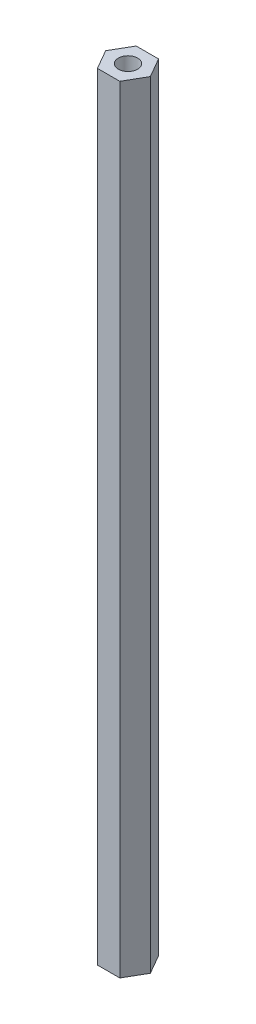
SolidWorks part; units mm, degrees
material "6061-T6 (SS)"
ref_plane "Front" through (0, 0, 0) normal (0, 0, 1) x (1, 0, 0)
ref_plane "Top" through (0, 0, 0) normal (0, 1, 0) x (1, 0, 0)
ref_plane "Right" through (0, 0, 0) normal (1, 0, 0) x (0, 0, -1)
sketch "Sketch1" plane through (0, 0, 0) normal (0, 1, 0) x (1, 0, 0)
  line L1 (2.8868, 0) -> (1.4434, 2.5)
  line L2 (1.4434, 2.5) -> (-1.4434, 2.5)
  line L3 (-1.4434, 2.5) -> (-2.8868, 0)
  line L4 (-2.8868, 0) -> (-1.4434, -2.5)
  line L5 (-1.4434, -2.5) -> (1.4434, -2.5)
  line L6 (1.4434, -2.5) -> (2.8868, 0)
  circle A0 centre (0, 0) radius 2.5 construction
  dimension "D1" = 5
extrude "Boss-Extrude1" add sketch "Sketch1" along normal mid plane 100.203
ref_axis "Axis1" through (0, 49.5981, 0) along (0, -1, 0)
sketch "Sketch4" plane through (0, 50.1015, 0) normal (0, 1, 0) x (1, 0, 0)
  point P0 (0, 0)
hole_wizard "M3x0.5 Tapped Hole1" positions "Sketch4" profile "Sketch3" tap size "M3x0.5" standard "ANSI Metric"
cosmetic thread "Hole Thread1" parameters "D2"=3
sketch "Sketch3" plane through (0, 50.1015, 0) normal (1, 0, 0) x (0, 0, 1)
  line L0 (0, 0) -> (0, 10.2761)
  line L1 (0, 10.2761) -> (1.25, 9.525)
  line L2 (1.25, 9.525) -> (1.25, 0)
  line L5 (1.25, 0) -> (0, 0)
  line L10 (0, 10.2761) -> (-1.25, 9.525) construction
  line L11 (0, -6.35) -> (0, 107.95) construction
  dimension "Tap Drill Dia." = 2.5
  dimension "Tap Drill Depth" = 9.525
  dimension "Drill Angle" = 118
mirror "Mirror1" about plane through (0, 0, 0) normal (0, 1, 0) of "M3x0.5 Tapped Hole1"
cosmetic thread "Hole Thread2" parameters "D1"=100.203, "D2"=3
